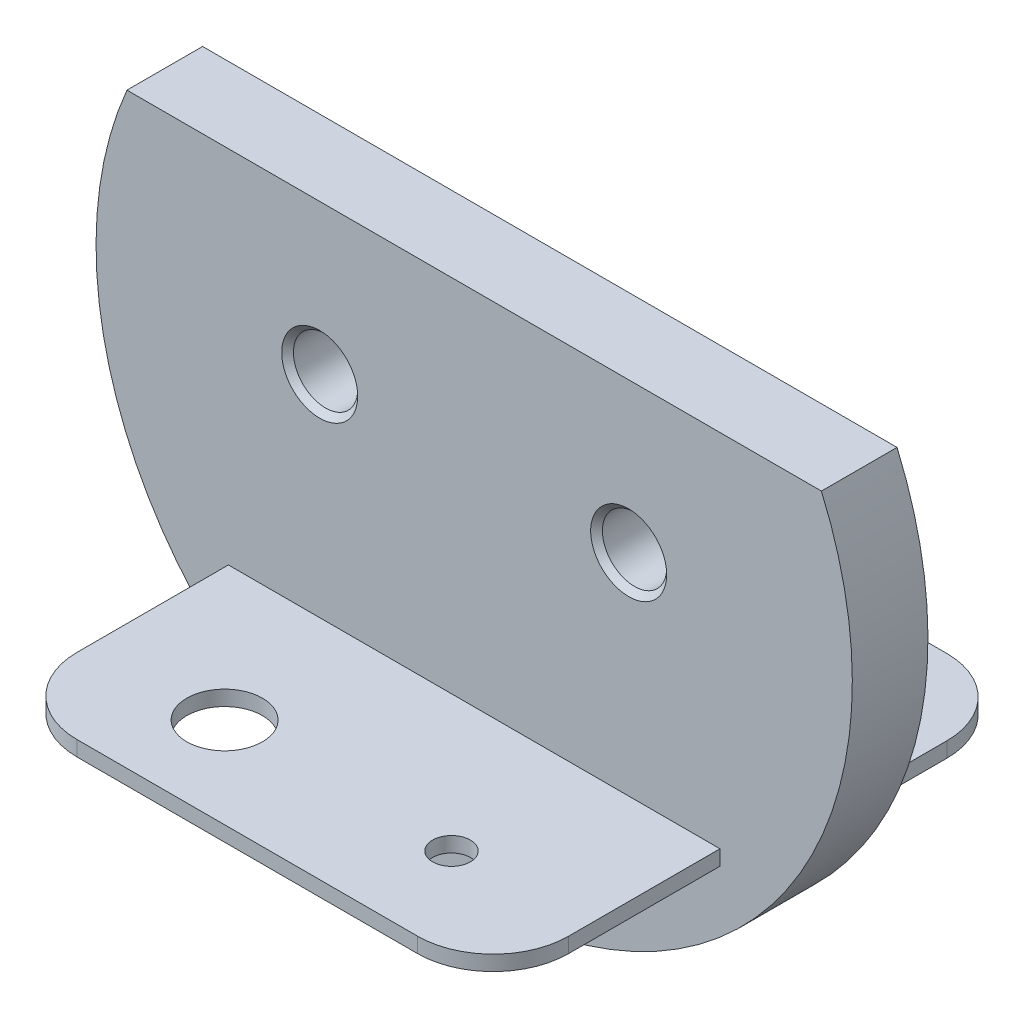
SolidWorks part; units mm, degrees
ref_plane "前视基准面" through (0, 0, 0) normal (0, 0, 1) x (1, 0, 0)
ref_plane "上视基准面" through (0, 0, 0) normal (0, 1, 0) x (1, 0, 0)
ref_plane "右视基准面" through (0, 0, 0) normal (1, 0, 0) x (0, 0, -1)
sketch "草图1" plane through (0, 0, 0) normal (0, 0, 1) x (1, 0, 0)
  circle A0 centre (0, 0) radius 50
  dimension "D1" = 100
extrude "凸台-拉伸1" add sketch "草图1" along normal blind 10
hole_wizard "M10 螺纹孔1" positions "草图7" profile "草图8" tap size "M10" standard "GB" end condition through all
sketch "草图7" plane through (0, 0, 10) normal (0, 0, 1) x (1, 0, 0)
  point P0 (-20.4267, 0)
sketch "草图8" plane through (-20.4267, 0, 10) normal (1, 0, 0) x (0, -1, 0)
  line L0 (0, 0) -> (0, 10)
  line L1 (0, 10) -> (4.25, 10)
  line L2 (4.25, 10) -> (4.25, 0.775)
  line L3 (4.25, 0.775) -> (5.025, 0)
  line L5 (5.025, 0) -> (0, 0)
  line L6 (-4.25, 0.775) -> (-5.025, 0) construction
  line L11 (0, -6.35) -> (0, 107.95) construction
  dimension "通孔螺纹孔钻头直径" = 8.5
  dimension "通孔螺纹孔钻头深度" = 10
  dimension "近端锥形沉头孔直径" = 10.05
  dimension "近端锥形沉头孔角度" = 90
cosmetic thread "孔螺蚊线1" parameters "D2"=10
mirror "镜向2" about plane through (0, 0, 0) normal (1, 0, 0) of "M10 螺纹孔1"
cosmetic thread "孔螺蚊线2" parameters "D2"=10
sketch "草图16" plane through (0, 0, 10) normal (0, 0, 1) x (1, 0, 0)
  line L0 (-32.5, -29.8649) -> (32.5, -29.8649)
  line L5 (-32.5, -29.8649) -> (32.5, 29.8649) construction
  line L6 (-32.5, 29.8649) -> (32.5, -29.8649) construction
  line L7 (-82.8685, 7.8026) -> (-82.0717, 7.2067)
  line L8 (32.5, -29.8649) -> (32.5, -27.8649)
  line L9 (-32.5, -29.8649) -> (-32.5, -27.8649)
  line L10 (-32.5, -27.8649) -> (32.5, -27.8649)
  point P0 (0, 0)
  dimension "D1" = 65
  dimension "D2" = 2
  dimension "D3" = 65
extrude "凸台-拉伸2" add sketch "草图16" along normal blind 30 contours L10 L9 L0 L8 region at (0, -28.8649, 10)
fillet "圆角2" radius 10 2 edges at (32.5, -28.8649, 40) (-32.5, -28.8649, 40)
sketch "草图20" plane through (0, -29.8649, 0) normal (0, -1, 0) x (1, 0, 0)
  line L0 (0, 0) -> (0, 42.4229) construction
  line L1 (-22.5, 40) -> (22.5, 40) construction
  circle A0 centre (-15, 28) radius 5
  circle A1 centre (15, 28) radius 2.5
  dimension "D1" = 12
  dimension "D4" = 10
  dimension "D5" = 5
  dimension "D2" = 42.4229
  dimension "D3" = 15
extrude "切除-拉伸1" cut sketch "草图20" against normal up to next
sketch "草图24" plane through (0, -27.8649, 0) normal (0, 1, 0) x (1, 0, 0)
sketch "草图27" plane through (0, 0, 0) normal (0, 0, -1) x (-1, 0, 0)
  line L0 (-32.5, -30.5) -> (32.5, -30.5)
  line L2 (32.5, -30.5) -> (32.5, -32.5)
  line L3 (32.5, -32.5) -> (-32.5, -32.5)
  line L4 (-32.5, -30.5) -> (-32.5, -32.5)
  line L5 (32.5, 32.5) -> (-32.5, -32.5) construction
  line L6 (32.5, -32.5) -> (-32.5, 32.5) construction
  point P0 (0, 0)
  dimension "D1" = 65
  dimension "D2" = 2
extrude "凸台-拉伸3" add sketch "草图27" along normal blind 30
fillet "圆角4" radius 10 2 edges at (-32.5, -31.5, -30) (32.5, -31.5, -30)
sketch "草图29" plane through (0, -30.5, 0) normal (0, 1, 0) x (1, 0, 0)
  line L0 (0, 0) -> (0, 30) construction
  line L1 (-22.5, 30) -> (22.5, 30) construction
  circle A1 centre (-15, 15.2707) radius 2.5
  circle A2 centre (15, 15.2707) radius 2.5
  dimension "D2" = 5
  dimension "D1" = 30
extrude "切除-拉伸2" cut sketch "草图29" against normal through all
sketch "草图30" plane through (0, 0, 0) normal (0, 0, -1) x (-1, 0, 0)
  line L0 (-45.9117, 19.802) -> (45.9117, 19.802)
  circle A0 centre (0, 0) radius 50 construction
  arc A1 (-45.9117, 19.802) -> (45.9117, 19.802) centre (0, 0) cw
extrude "切除-拉伸3" cut sketch "草图30" against normal through all
